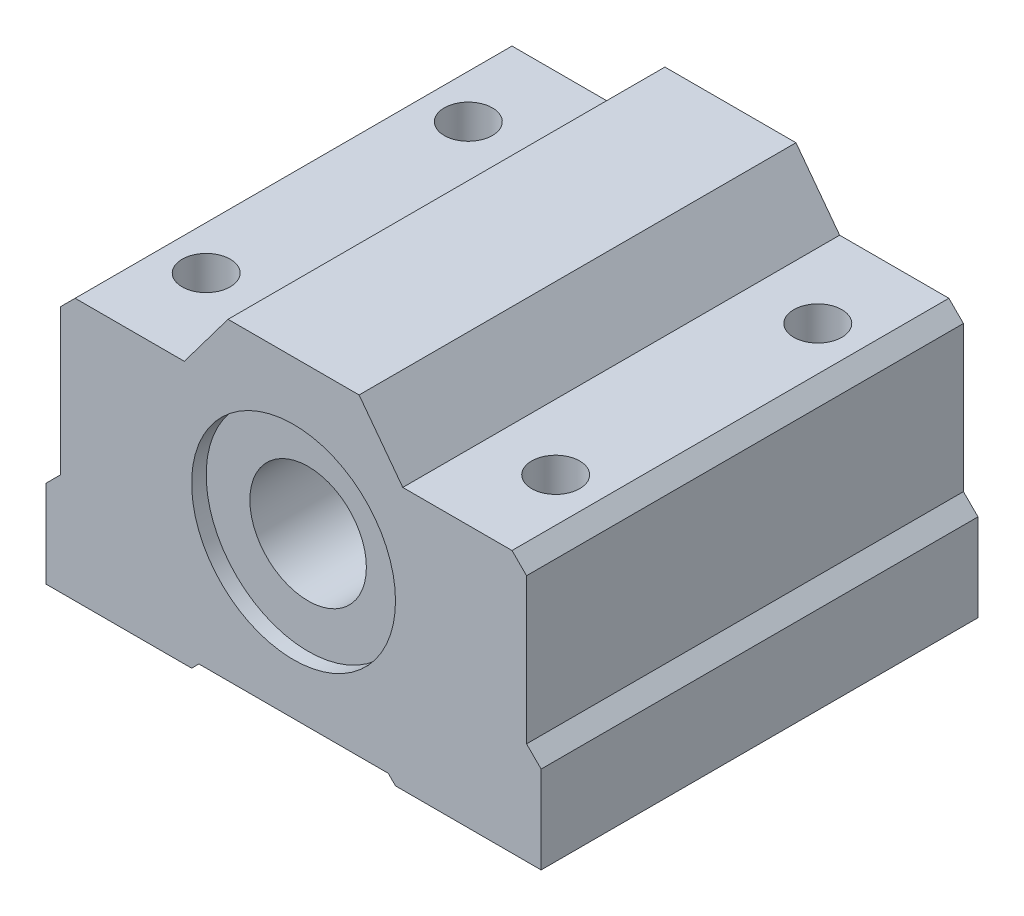
SolidWorks part; units mm, degrees
ref_plane "Front" through (0, 0, 0) normal (0, 0, 1) x (1, 0, 0)
ref_plane "Top" through (0, 0, 0) normal (0, 1, 0) x (1, 0, 0)
ref_plane "Right" through (0, 0, 0) normal (1, 0, 0) x (0, 0, -1)
sketch "Sketch1" plane through (0, 0, 0) normal (0, 0, 1) x (1, 0, 0)
  line L2 (-17, -2.4052) -> (-17, -8.4052)
  line L3 (-17, -8.4052) -> (-7, -8.4052)
  line L4 (-7, -8.4052) -> (-6.5, -7.9052)
  line L5 (-6.5, -7.9052) -> (6.5, -7.9052)
  line L6 (6.5, -7.9052) -> (7, -8.4052)
  line L7 (-17, -2.4052) -> (-16, -1.4052)
  line L8 (7, -8.4052) -> (17, -8.4052)
  line L9 (17, -8.4052) -> (17, -2.4052)
  line L15 (-16, -1.4052) -> (-16, 8.5948)
  line L16 (-16, 8.5948) -> (-15, 9.5948)
  line L17 (-15, 9.5948) -> (-7.5, 9.5948)
  line L21 (7.5, 9.5948) -> (15, 9.5948)
  line L22 (15, 9.5948) -> (16, 8.5948)
  line L23 (16, 8.5948) -> (16, -1.4052)
  line L24 (16, -1.4052) -> (17, -2.4052)
  line L25 (-7.5, 9.5948) -> (-4.5, 13.5948)
  line L26 (-4.5, 13.5948) -> (4.5, 13.5948)
  line L27 (4.5, 13.5948) -> (7.5, 9.5948)
  point P0 (0, -7.9052)
  point P19 (0, 3.0948)
  point P20 (0, 0)
  dimension "D1" = 34
  dimension "D2" = 32
  dimension "D3" = 0.5
  dimension "D4" = 10
  dimension "D5" = 0.5
  dimension "D6" = 6
  dimension "D7" = 15
  dimension "D8" = 30
  dimension "D9" = 9
  dimension "D10" = 22
  dimension "D11" = 18
  dimension "D12" = 11
extrude "Boss-Extrude1" add sketch "Sketch1" along normal blind 30
sketch "Sketch2" plane through (0, 0, 0) normal (0, 0, -1) x (-1, 0, 0)
  line L0 (17, -8.4052) -> (7, -8.4052) construction
  line L1 (6.5, -7.9052) -> (-6.5, -7.9052) construction
  circle A0 centre (0, 2.5948) radius 4
  point P4 (0, 0)
  point P7 (0, -7.9052)
  dimension "D1" = 8
  dimension "D2" = 11
extrude "Cut-Extrude1" cut sketch "Sketch2" against normal through all
sketch "Sketch3" plane through (0, 0, 0) normal (0, 0, -1) x (-1, 0, 0)
  circle A0 centre (0, 2.5948) radius 7
  dimension "D1" = 14
extrude "Cut-Extrude2" cut sketch "Sketch3" against normal blind 1
sketch "Sketch4" plane through (0, 0, 30) normal (0, 0, 1) x (1, 0, 0)
  circle A1 centre (0, 2.5948) radius 7
  circle A2 centre (0, 2.5948) radius 7
  dimension "D1" = 0
extrude "Cut-Extrude3" cut sketch "Sketch4" against normal blind 1
sketch "Sketch5" plane through (0, -8.4052, 0) normal (0, -1, 0) x (1, 0, 0)
  line L1 (-12, 24) -> (12, 24) construction
  line L2 (-12, 24) -> (-12, 6) construction
  line L3 (-12, 6) -> (12, 6) construction
  line L4 (12, 24) -> (12, 6) construction
  line L5 (-12, 24) -> (12, 6) construction
  line L6 (-12, 6) -> (12, 24) construction
  line L10 (-6.5, 0) -> (6.5, 0)
  line L11 (6.5, 0) -> (6.5, 30)
  line L12 (6.5, 30) -> (-6.5, 30)
  line L13 (-6.5, 30) -> (-6.5, 0)
  line L14 (-6.5, 0) -> (6.5, 0)
  line L15 (6.5, 0) -> (6.5, 30)
  line L16 (6.5, 30) -> (-6.5, 30)
  line L17 (-6.5, 30) -> (-6.5, 0)
  point P0 (0, 15)
  point P5 (0, 0)
  point P8 (0, 0)
  point P10 (-6.5, 15)
  point P12 (0, 0)
  point P13 (0, 0)
  dimension "D1" = 24
  dimension "D2" = 18
  dimension "D3" = 0
hole_wizard "Tap Drill for M4x0.7 Tap1" positions "Sketch6" profile "Sketch7" hole size "M4x0.7" standard "ANSI Metric" end condition through all
sketch "Sketch6" plane through (0, -8.4052, 0) normal (0, -1, 0) x (-1, 0, 0)
  point P0 (-12, -6)
  point P3 (12, -6)
  point P6 (12, -24)
  point P9 (-12, -24)
sketch "Sketch7" plane through (12, -8.4052, 6) normal (1, 0, 0) x (0, 0, -1)
  line L0 (0, 0) -> (0, 22)
  line L1 (0, 22) -> (1.65, 22)
  line L2 (1.65, 22) -> (1.65, 0)
  line L5 (1.65, 0) -> (0, 0)
  line L11 (0, -6.35) -> (0, 107.95) construction
  dimension "Thru Hole Dia." = 3.3
  dimension "Thru Hole Depth" = 22
